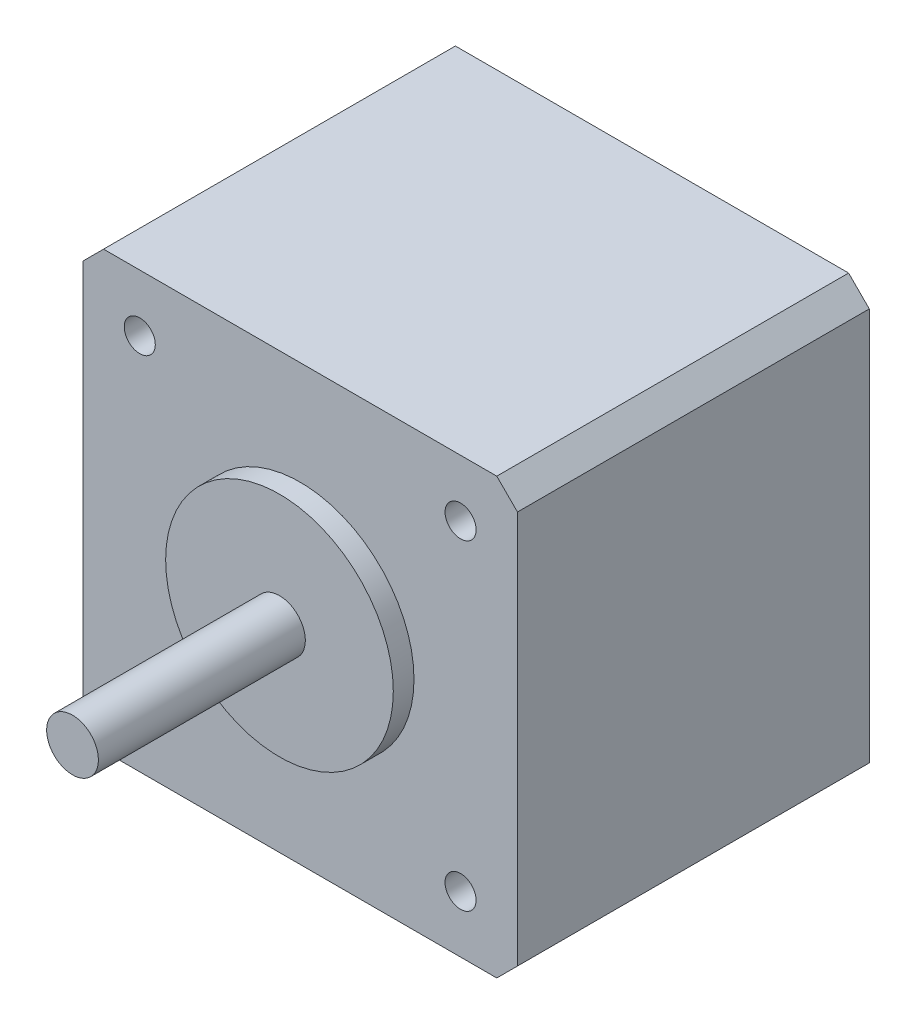
SolidWorks part; units mm, degrees
ref_plane "정면" through (0, 0, 0) normal (0, 0, 1) x (1, 0, 0)
ref_plane "윗면" through (0, 0, 0) normal (0, 1, 0) x (1, 0, 0)
ref_plane "우측면" through (0, 0, 0) normal (1, 0, 0) x (0, 0, -1)
sketch "스케치1" plane through (0, 0, 0) normal (0, 0, 1) x (1, 0, 0)
  line L1 (-21, 21) -> (21, 21)
  line L2 (-21, 21) -> (-21, -21)
  line L3 (-21, -21) -> (21, -21)
  line L4 (21, 21) -> (21, -21)
  line L5 (-21, 21) -> (21, -21) construction
  line L6 (-21, -21) -> (21, 21) construction
  line L7 (-15.5, 15.5) -> (15.5, 15.5) construction
  line L8 (-15.5, 15.5) -> (-15.5, -15.5) construction
  line L9 (-15.5, -15.5) -> (15.5, -15.5) construction
  line L10 (15.5, 15.5) -> (15.5, -15.5) construction
  line L11 (-15.5, 15.5) -> (15.5, -15.5) construction
  line L12 (-15.5, -15.5) -> (15.5, 15.5) construction
  circle A0 centre (0, 0) radius 11
  circle A1 centre (0, 0) radius 2.5
  circle A2 centre (15.5, 15.5) radius 1.5
  circle A3 centre (-15.5, 15.5) radius 1.5
  circle A4 centre (-15.5, -15.5) radius 1.5
  circle A5 centre (15.5, -15.5) radius 1.5
  point P0 (0, 0)
  point P6 (0, 0)
  dimension "D5" = 3
  dimension "D6" = 22
  dimension "D7" = 5
  dimension "D1" = 42
  dimension "D2" = 42
  dimension "D3" = 31
  dimension "D4" = 31
extrude "보스-돌출1" add sketch "스케치1" against normal blind 34 contours L4 L1 L2 L3 A5 A4 A3 A2 A0 | A0 A1 | A1 region at (0, 20.406, 0) region at (-10.6889, 0, 0) region at (0, 0, 0)
extrude "보스-돌출2" add sketch "스케치1<3>" along normal blind 2 contours A0 A1 | A1 region at (-10.6889, 0, 0) region at (0, 0, 0)
sketch "스케치1<3>" plane through (0, 0, 0) normal (0, 0, 1) x (1, 0, 0) same geometry as "스케치1"
extrude "보스-돌출3" add sketch "스케치1<4>" along normal blind 22 contours A1 region at (0, 0, 0)
sketch "스케치1<4>" plane through (0, 0, 0) normal (0, 0, 1) x (1, 0, 0) same geometry as "스케치1"
chamfer "모따기1" distance 2 angle 45 4 edges at (-21, 21, -17) (21, 21, -17) (21, -21, -17) (-21, -21, -17)
